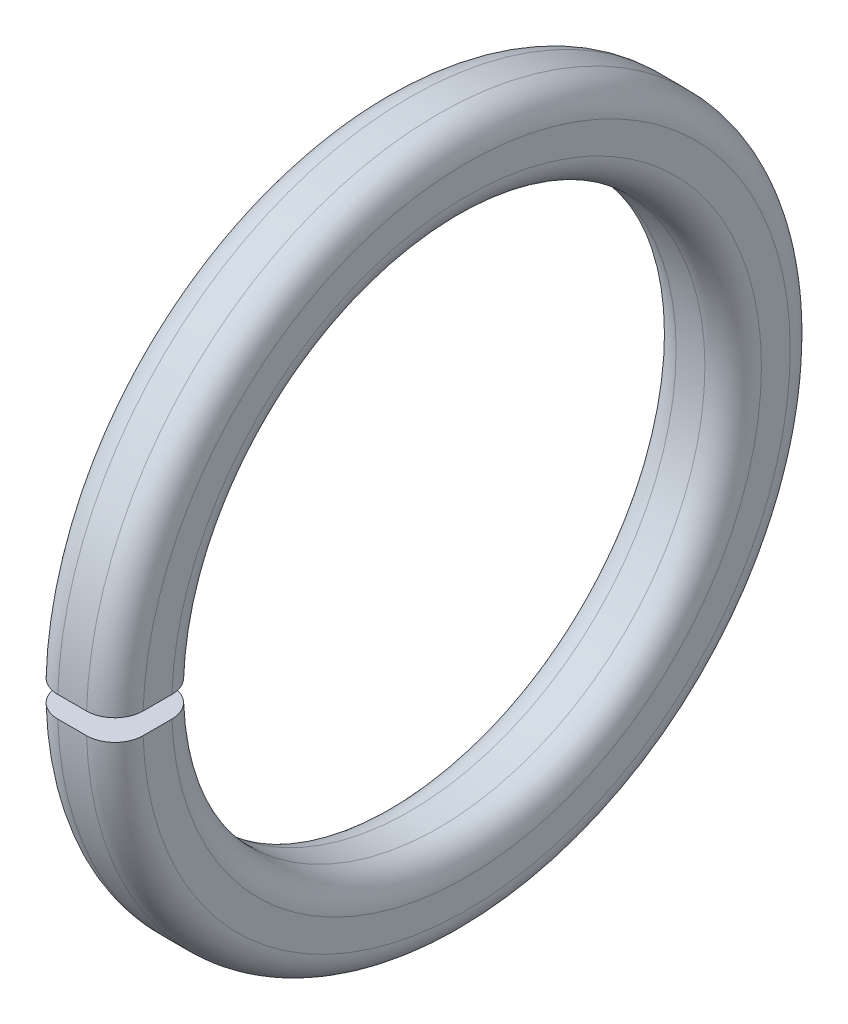
SolidWorks part; units mm, degrees
ref_plane "Plane1" through (0, 0, 0) normal (0, 0, 1) x (1, 0, 0)
ref_plane "Plane2" through (0, 0, 0) normal (0, 1, 0) x (1, 0, 0)
ref_plane "Plane3" through (0, 0, 0) normal (1, 0, 0) x (0, 0, -1)
sketch "Sketch1" plane through (0, 0, 0) normal (0, 0, 1) x (1, 0, 0)
  line L0 (-34.925, 0) -> (9.525, 0) construction
  line L1 (0, 27.65) -> (0, 30.35)
  line L2 (-2.65, 33) -> (-5.35, 33)
  line L3 (-8, 30.35) -> (-8, 27.65)
  line L4 (-5.35, 25) -> (-2.65, 25)
  arc A0 (-5.35, 25) -> (-8, 27.65) centre (-5.35, 27.65) cw
  arc A1 (0, 27.65) -> (-2.65, 25) centre (-2.65, 27.65) cw
  arc A2 (0, 30.35) -> (-2.65, 33) centre (-2.65, 30.35) ccw
  arc A3 (-5.35, 33) -> (-8, 30.35) centre (-5.35, 30.35) ccw
  point P8 (-8, 25)
  point P14 (0, 33)
  point P17 (-8, 33)
  dimension "Thickness" = 8
revolve "Base-Revolve" add sketch "Sketch1" angle 360 about L0
sketch "Sketch2" plane through (0, 0, 0) normal (-1, 0, 0) x (0, -1, 0)
  line L0 (-1, 0) -> (1, 0)
  line L1 (0, 0) -> (0, 12.7) construction
  line L2 (1, 0) -> (1, 33.66)
  line L3 (1, 33.66) -> (-1, 33.66)
  line L4 (-1, 33.66) -> (-1, 0)
  dimension "D1" = 2
  dimension "D2" = 33.66
extrude "Gap" cut sketch "Sketch2" along normal through all
equation "\"D1@Sketch2\" = \"Thickness@Sketch1\" * 0.25"
equation "\"Outside_dia@Sketch1\" = \"Inside_dia@Sketch1\" + 2.0 * \"Thickness@Sketch1\""
equation "\"D2@Sketch2\" = \"Outside_dia@Sketch1\" * 0.51"
